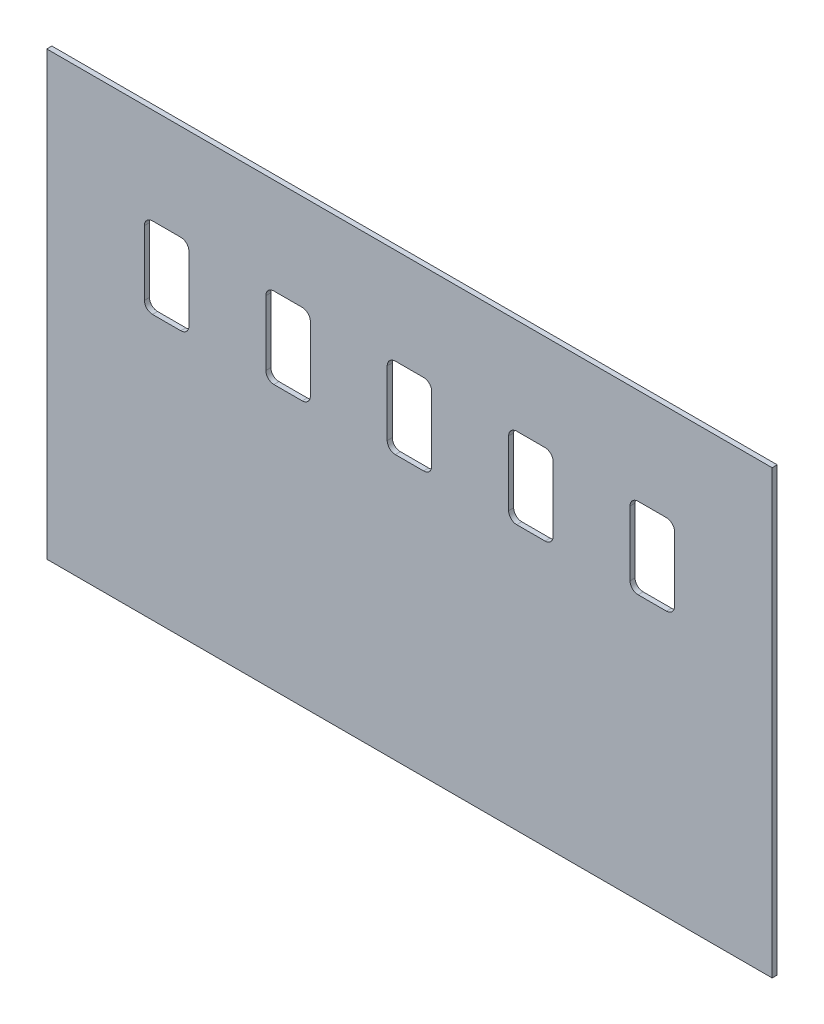
SolidWorks part; units mm, degrees
ref_plane "Front Plane" through (0, 0, 0) normal (0, 0, 1) x (1, 0, 0)
ref_plane "Top Plane" through (0, 0, 0) normal (0, 1, 0) x (1, 0, 0)
ref_plane "Right Plane" through (0, 0, 0) normal (1, 0, 0) x (0, 0, -1)
sketch "Sketch1" plane through (0, 0, 0) normal (0, 0, 1) x (1, 0, 0)
  line L1 (-227.6475, -138.684) -> (227.6475, -138.684)
  line L2 (-227.6475, -138.684) -> (-227.6475, 138.684)
  line L3 (-227.6475, 138.684) -> (227.6475, 138.684)
  line L4 (227.6475, -138.684) -> (227.6475, 138.684)
  line L5 (0, 138.684) -> (0, -138.684) construction
  line L6 (-227.6475, 0) -> (227.6475, 0) construction
  point P0 (0, 0)
  point P4 (-159.0675, 0)
  point P5 (159.0675, 0)
  point P6 (0, 97.0788)
  point P7 (0, -97.0788)
  dimension "Width" = 277.368
  dimension "Break" = 68.58
  dimension "D2" = 68.58
  dimension "D1" = 41.6052
  dimension "D3" = 41.6052
  dimension "D4" = 455.295
sketch "Sketch2" plane through (0, 0, 0) normal (1, 0, 0) x (0, 0, -1)
  line L0 (-1.5875, -138.684) -> (1.5875, -138.684)
  dimension "Thickness" = 3.175
sketch "Sketch3" plane through (0, 0, 0) normal (0, 0, 1) x (1, 0, 0)
  line L0 (-227.6475, -138.684) -> (-227.6475, 138.684) construction
  line L1 (-227.6475, -138.684) -> (227.6475, -138.684) construction
  line L2 (227.6475, -138.684) -> (227.6475, 138.684) construction
  line L3 (-227.6475, 138.684) -> (227.6475, 138.684) construction
  line L4 (-227.6475, -138.684) -> (-227.6475, 138.684)
  line L5 (-227.6475, -138.684) -> (227.6475, -138.684)
  line L6 (227.6475, -138.684) -> (227.6475, 138.684)
  line L7 (-227.6475, 138.684) -> (227.6475, 138.684)
extrude "Boss-Extrude1" add sketch "Sketch3" along normal mid plane 3.175
sketch "Sketch4" plane through (0, 0, 1.5875) normal (0, 0, 1) x (1, 0, 0)
  line L0 (-227.6475, 52.959) -> (-158.75, 52.959) construction
  line L1 (-82.55, 52.959) -> (-82.55, 78.359) construction
  line L2 (-82.55, 78.359) -> (-90.17, 78.359) construction
  line L3 (-158.75, 52.959) -> (-158.75, 78.359) construction
  line L6 (-227.6475, -105.791) -> (-227.6475, 52.959) construction
  line L7 (-227.6475, -115.316) -> (-227.6475, 138.684) construction
  line L8 (-158.75, 52.959) -> (-82.55, 52.959) construction
  line L9 (-82.55, 52.959) -> (-6.35, 52.959) construction
  line L10 (-6.35, 52.959) -> (69.85, 52.959) construction
  line L11 (69.85, 52.959) -> (146.05, 52.959) construction
  line L12 (-82.55, 52.959) -> (-82.55, 27.559) construction
  line L13 (-82.55, 27.559) -> (-62.23, 27.559) construction
  line L16 (-158.75, 78.359) -> (-166.37, 78.359) construction
  line L17 (-158.75, 52.959) -> (-158.75, 27.559) construction
  line L18 (-158.75, 27.559) -> (-138.43, 27.559) construction
  line L19 (-6.35, 52.959) -> (-6.35, 78.359) construction
  line L20 (-161.29, 78.359) -> (-143.51, 78.359)
  line L21 (-166.37, 73.279) -> (-166.37, 32.639)
  line L22 (-161.29, 27.559) -> (-143.51, 27.559)
  line L23 (-138.43, 73.279) -> (-138.43, 32.639)
  line L24 (-6.35, 78.359) -> (-13.97, 78.359) construction
  line L25 (-6.35, 52.959) -> (-6.35, 27.559) construction
  line L26 (-6.35, 27.559) -> (13.97, 27.559) construction
  line L27 (69.85, 52.959) -> (69.85, 78.359) construction
  line L28 (-8.89, 78.359) -> (8.89, 78.359)
  line L29 (-13.97, 73.279) -> (-13.97, 32.639)
  line L30 (-8.89, 27.559) -> (8.89, 27.559)
  line L31 (13.97, 73.279) -> (13.97, 32.639)
  line L32 (69.85, 78.359) -> (62.23, 78.359) construction
  line L33 (69.85, 52.959) -> (69.85, 27.559) construction
  line L34 (69.85, 27.559) -> (90.17, 27.559) construction
  line L35 (146.05, 52.959) -> (146.05, 78.359) construction
  line L36 (67.31, 78.359) -> (85.09, 78.359)
  line L37 (62.23, 73.279) -> (62.23, 32.639)
  line L38 (67.31, 27.559) -> (85.09, 27.559)
  line L39 (90.17, 73.279) -> (90.17, 32.639)
  line L40 (146.05, 78.359) -> (138.43, 78.359) construction
  line L41 (146.05, 52.959) -> (146.05, 27.559) construction
  line L42 (146.05, 27.559) -> (166.37, 27.559) construction
  line L44 (143.51, 78.359) -> (161.29, 78.359)
  line L45 (138.43, 73.279) -> (138.43, 32.639)
  line L46 (143.51, 27.559) -> (161.29, 27.559)
  line L47 (166.37, 73.279) -> (166.37, 32.639)
  line L48 (-85.09, 78.359) -> (-67.31, 78.359)
  line L49 (-90.17, 73.279) -> (-90.17, 32.639)
  line L50 (-85.09, 27.559) -> (-67.31, 27.559)
  line L51 (-62.23, 73.279) -> (-62.23, 32.639)
  arc A0 (138.43, 32.639) -> (143.51, 27.559) centre (143.51, 32.639) ccw
  arc A1 (166.37, 32.639) -> (161.29, 27.559) centre (161.29, 32.639) cw
  arc A2 (161.29, 78.359) -> (166.37, 73.279) centre (161.29, 73.279) cw
  arc A3 (138.43, 73.279) -> (143.51, 78.359) centre (143.51, 73.279) cw
  arc A4 (62.23, 32.639) -> (67.31, 27.559) centre (67.31, 32.639) ccw
  arc A5 (90.17, 32.639) -> (85.09, 27.559) centre (85.09, 32.639) cw
  arc A6 (85.09, 78.359) -> (90.17, 73.279) centre (85.09, 73.279) cw
  arc A7 (67.31, 78.359) -> (62.23, 73.279) centre (67.31, 73.279) ccw
  arc A8 (-13.97, 32.639) -> (-8.89, 27.559) centre (-8.89, 32.639) ccw
  arc A9 (13.97, 32.639) -> (8.89, 27.559) centre (8.89, 32.639) cw
  arc A10 (8.89, 78.359) -> (13.97, 73.279) centre (8.89, 73.279) cw
  arc A11 (-8.89, 78.359) -> (-13.97, 73.279) centre (-8.89, 73.279) ccw
  arc A15 (-138.43, 32.639) -> (-143.51, 27.559) centre (-143.51, 32.639) cw
  arc A16 (-143.51, 78.359) -> (-138.43, 73.279) centre (-143.51, 73.279) cw
  arc A17 (-166.37, 73.279) -> (-161.29, 78.359) centre (-161.29, 73.279) cw
  arc A18 (-166.37, 32.639) -> (-161.29, 27.559) centre (-161.29, 32.639) ccw
  arc A19 (-90.17, 32.639) -> (-85.09, 27.559) centre (-85.09, 32.639) ccw
  arc A20 (-62.23, 32.639) -> (-67.31, 27.559) centre (-67.31, 32.639) cw
  arc A21 (-67.31, 78.359) -> (-62.23, 73.279) centre (-67.31, 73.279) cw
  arc A22 (-85.09, 78.359) -> (-90.17, 73.279) centre (-85.09, 73.279) ccw
  point P14 (-152.4, 78.359)
  point P15 (0, 0)
  point P16 (-76.2, 78.359)
  point P17 (-90.17, 52.959)
  point P18 (-13.97, 52.959)
  point P95 (62.23, 52.959)
  point P96 (138.43, 52.959)
  point P97 (0, 78.359)
  point P98 (76.2, 78.359)
  point P99 (152.4, 78.359)
  point P107 (-166.37, 52.959)
  dimension "D1" = 5.08
  dimension "D2" = 5.08
  dimension "D8" = 27.94
  dimension "D9" = 27.94
  dimension "D10" = 27.94
  dimension "D11" = 27.94
  dimension "D12" = 27.94
  dimension "D3" = 76.2
  dimension "D4" = 76.2
  dimension "D5" = 152.4
  dimension "D6" = 152.4
extrude "Cut-Extrude1" cut sketch "Sketch4" against normal blind 25.4 contours L21 A18 L22 A15 L23 A16 L20 A17 | A22 L48 A21 L51 A20 L50 A19 L49 | L29 A8 L30 A9 L31 A10 L28 A11 | L37 A4 L38 A5 L39 A6 L36 A7 | A3 L44 A2 L47 A1 L46 A0 L45
equation "\"D1@Boss-Extrude1\" = \"Thickness@Sketch2\""
equation "\"D2@Sketch1\" = \"Break@Sketch1\""
equation "\"D1@Sketch1\"=\"Width@Sketch1\"*0.15"
equation "\"D3@Sketch1\"=\"D1@Sketch1\""
equation "\"SlotWidth\"= 1.1in"
equation "\"D8@Sketch4\"=\"SlotWidth\""
equation "\"D9@Sketch4\"=\"SlotWidth\""
equation "\"D10@Sketch4\"=\"SlotWidth\""
equation "\"D11@Sketch4\"=\"SlotWidth\""
equation "\"D12@Sketch4\"=\"SlotWidth\""
